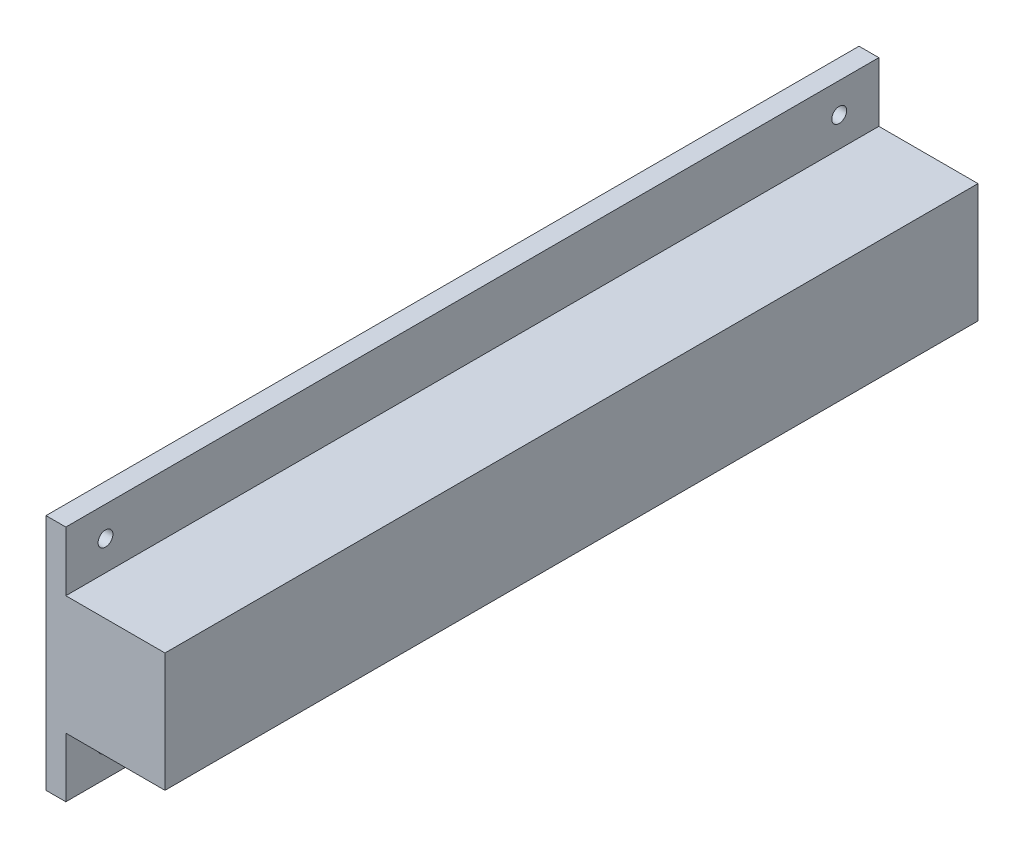
SolidWorks part; units mm, degrees
material "ABS"
ref_plane "Front Plane" through (0, 0, 0) normal (0, 0, 1) x (1, 0, 0)
ref_plane "Top Plane" through (0, 0, 0) normal (0, 1, 0) x (1, 0, 0)
ref_plane "Right Plane" through (0, 0, 0) normal (1, 0, 0) x (0, 0, -1)
sketch "Sketch1" plane through (0, 0, 0) normal (1, 0, 0) x (0, 0, -1)
  line L1 (-65.0875, 9.525) -> (65.0875, 9.525)
  line L2 (-65.0875, 9.525) -> (-65.0875, -9.525)
  line L3 (-65.0875, -9.525) -> (65.0875, -9.525)
  line L4 (65.0875, 9.525) -> (65.0875, -9.525)
  line L5 (-65.0875, 9.525) -> (65.0875, -9.525) construction
  line L6 (-65.0875, -9.525) -> (65.0875, 9.525) construction
  point P0 (0, 0)
  dimension "D1" = 130.175
  dimension "D2" = 19.05
extrude "Boss-Extrude1" add sketch "Sketch1" along normal blind 19.05
sketch "Sketch2" plane through (0, 0, 65.0875) normal (0, 0, 1) x (1, 0, 0)
  line L1 (0, 19.05) -> (3.175, 19.05)
  line L2 (0, 19.05) -> (0, -19.05)
  line L3 (0, -19.05) -> (3.175, -19.05)
  line L4 (3.175, 19.05) -> (3.175, -19.05)
  point P4 (0, 0)
  dimension "D1" = 38.1
  dimension "D2" = 3.175
extrude "Boss-Extrude2" add sketch "Sketch2" against normal up to surface (130.175 mm away) up to face at (9.525, 0, -65.0875)
sketch "Sketch4" plane through (3.175, 0, 0) normal (1, 0, 0) x (0, 0, -1)
  line L0 (-65.0875, 0) -> (65.0875, 0) construction
  line L1 (-65.0875, 9.525) -> (-65.0875, -9.525) construction
  line L2 (65.0875, -9.525) -> (65.0875, 9.525) construction
  line L3 (-65.0875, -14.2875) -> (65.0875, -14.2875) construction
  line L4 (-65.0875, -19.05) -> (-65.0875, -9.525) construction
  line L5 (65.0875, -9.525) -> (65.0875, -19.05) construction
  line L6 (0, 19.05) -> (0, -19.05) construction
  line L7 (65.0875, 19.05) -> (-65.0875, 19.05) construction
  line L8 (65.0875, -19.05) -> (-65.0875, -19.05) construction
  circle A0 centre (-58.7375, -14.2875) radius 1.1906
  circle A1 centre (58.7375, -14.2875) radius 1.1906
  circle A2 centre (58.7375, 14.2875) radius 1.1906
  circle A3 centre (-58.7375, 14.2875) radius 1.1906
  dimension "D1" = 6.35
  dimension "D2" = 2.3813
extrude "Cut-Extrude1" cut sketch "Sketch4" against normal through all
